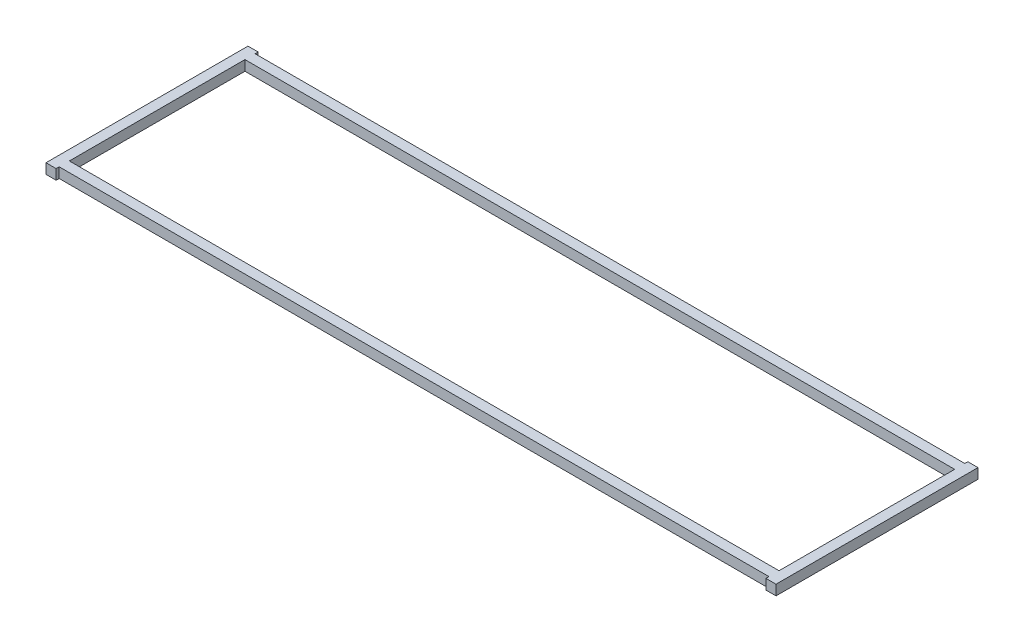
SolidWorks part; units mm, degrees
ref_plane "Front" through (0, 0, 0) normal (0, 0, 1) x (1, 0, 0)
ref_plane "Top" through (0, 0, 0) normal (0, 1, 0) x (1, 0, 0)
ref_plane "Right" through (0, 0, 0) normal (1, 0, 0) x (0, 0, -1)
sketch "Sketch1" plane through (0, 0, 0) normal (0, 1, 0) x (1, 0, 0)
  line L0 (222.25, 63.2523) -> (228.6, 63.2523)
  line L1 (-228.6, 63.2523) -> (-222.25, 63.2523)
  line L2 (-228.6, 63.2523) -> (-228.6, -63.2523)
  line L3 (-228.6, -63.2523) -> (-222.25, -63.2523)
  line L4 (228.6, 63.2523) -> (228.6, -63.2523)
  line L5 (-228.6, 63.2523) -> (228.6, -63.2523) construction
  line L6 (-228.6, -63.2523) -> (228.6, 63.2523) construction
  line L8 (-222.25, 63.2523) -> (-222.25, 61.3442)
  line L9 (-222.25, 61.3442) -> (222.25, 61.3442)
  line L10 (222.25, 63.2523) -> (222.25, 61.3442)
  line L12 (-222.25, -63.2523) -> (-222.25, -61.3442)
  line L13 (-222.25, -61.3442) -> (222.25, -61.3442)
  line L14 (222.25, -63.2523) -> (222.25, -61.3442)
  line L15 (222.25, -63.2523) -> (228.6, -63.2523)
  line L17 (-222.25, -54.9942) -> (222.25, -54.9942)
  line L18 (-222.25, -54.9942) -> (-222.25, 54.9942)
  line L19 (-222.25, 54.9942) -> (222.25, 54.9942)
  line L20 (222.25, -54.9942) -> (222.25, 54.9942)
  line L21 (-222.25, -54.9942) -> (222.25, 54.9942) construction
  line L22 (-222.25, 54.9942) -> (222.25, -54.9942) construction
  point P0 (0, 0)
  point P14 (0, 0)
  dimension "D1" = 457.2
  dimension "D2" = 126.5047
  dimension "D3" = 6.35
  dimension "D4" = 6.35
  dimension "D6" = 6.35
  dimension "D7" = 6.35
  dimension "D5" = 1.9082
extrude "Boss-Extrude1" add sketch "Sketch1" along normal blind 6.35
equation "\"D2@Sketch1\"    = (4.87075-.25) + 0.25 + ( 6 / 64 ) + 0.016"
